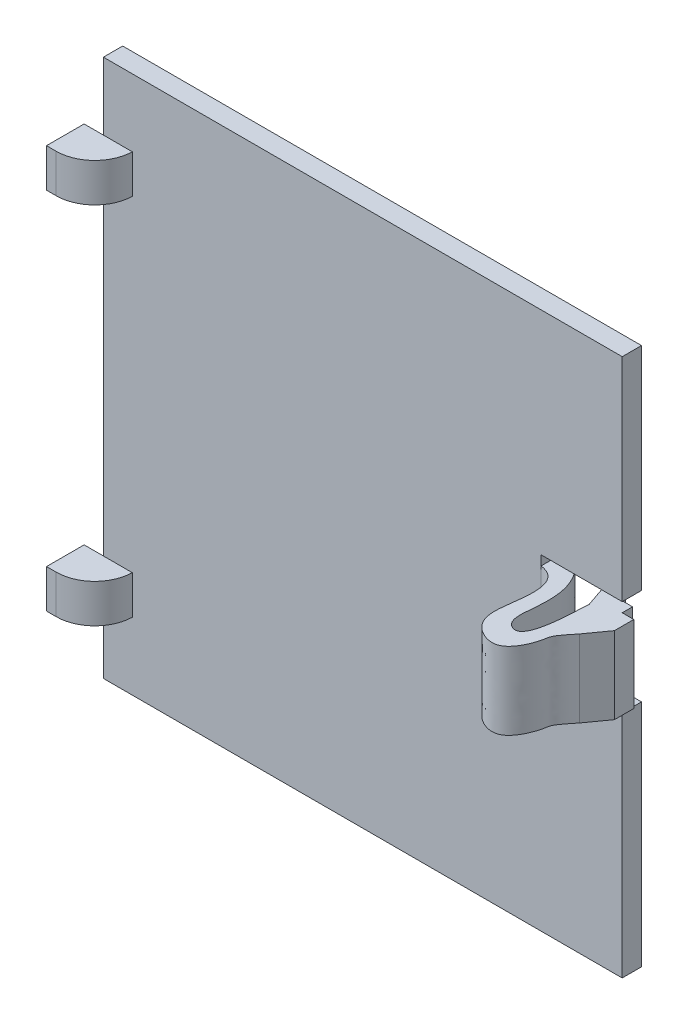
SolidWorks part; units mm, degrees
ref_plane "Plan de face" through (0, 0, 0) normal (0, 0, 1) x (1, 0, 0)
ref_plane "Plan de dessus" through (0, 0, 0) normal (0, 1, 0) x (1, 0, 0)
ref_plane "Plan de droite" through (0, 0, 0) normal (1, 0, 0) x (0, 0, -1)
sketch "Esquisse1" plane through (0, 0, 0) normal (0, 0, 1) x (1, 0, 0)
  line L1 (0, 0) -> (53.8, 0)
  line L2 (0, 0) -> (0, 55.8)
  line L3 (0, 55.8) -> (53.8, 55.8)
  line L4 (53.8, 0) -> (53.8, 55.8)
  dimension "D1" = 53.8
  dimension "D2" = 55.8
extrude "Boss.-Extru.1" add sketch "Esquisse1" along normal blind 2
sketch "Esquisse3" plane through (0, 0, 2) normal (0, 0, 1) x (1, 0, 0)
  line L0 (0, 55.8) -> (0, 0) construction
  line L1 (3, 7) -> (-2, 7)
  line L2 (3, 7) -> (3, 11)
  line L3 (3, 11) -> (-2, 11)
  line L4 (-2, 7) -> (-2, 11)
  line L5 (3, 44.8) -> (-2, 44.8)
  line L6 (3, 44.8) -> (3, 48.8)
  line L7 (3, 48.8) -> (-2, 48.8)
  line L8 (-2, 44.8) -> (-2, 48.8)
  line L9 (53.8, 55.8) -> (0, 55.8) construction
  line L10 (0, 0) -> (53.8, 0) construction
  dimension "D1" = 5
  dimension "D2" = 3
  dimension "D3" = 5
  dimension "D4" = 3
  dimension "D5" = 4
  dimension "D6" = 4
  dimension "D7" = 7
  dimension "D8" = 7
extrude "Boss.-Extru.2" add sketch "Esquisse3" along normal blind 3.9
fillet "Congé1" radius 4 2 edges at (3, 46.8, 5.9) (3, 9, 5.9)
sketch "Esquisse4" plane through (0, 0, 2) normal (0, 0, 1) x (1, 0, 0)
  line L0 (53.8, 0) -> (53.8, 55.8) construction
  line L1 (53.8, 33.8) -> (45.3874, 33.8)
  line L2 (53.8, 33.8) -> (53.8, 23.8)
  line L3 (53.8, 23.8) -> (45.3874, 23.8)
  line L4 (45.3874, 33.8) -> (45.3874, 23.8)
  line L5 (53.8, 55.8) -> (0, 55.8) construction
  dimension "D1" = 10
  dimension "D2" = 22
extrude "Enlèv. mat.-Extru.1" cut sketch "Esquisse4" against normal blind 7.8
sketch "Esquisse5" plane through (0, 33.8, 0) normal (0, -1, 0) x (1, 0, 0)
  line L0 (52.1165, 0.9275) -> (52.1165, 0)
  line L1 (0, 0) -> (53.8, 0) construction
  line L2 (52.1165, 0) -> (50.314, 0)
  line L3 (50.314, 0) -> (51.3364, 2.9673)
  line L4 (52.1165, 0.9275) -> (53.8, 0.9275)
  line L5 (53.8, 2) -> (53.8, 0) construction
  line L6 (53.8, 0.9275) -> (53.8, 2)
  line L7 (53.8, 2) -> (55, 2)
  line L8 (55, 2) -> (55, 4)
  line L9 (55, 4) -> (53.4886, 6.1084)
  line L10 (45.3874, 2) -> (45.3874, 0)
  spline S0 degree 3 poles (45.3874, 0) (46.455, 0.0308) (47.1256, -0.0213) (48.8996, 2.4805) (48.9573, 5.3687) (48.4914, 8.6027) (50.0819, 9.3139) (51.3612, 7.4414) (51.2508, 3.2239) (51.3364, 2.9673) knots 0 0 0 0 0.100125 0.177204 0.427984 0.587008 0.626059 0.727291 1 1 1 1
  spline S1 degree 3 poles (45.3874, 2) (47.5717, 2.2817) (47.4148, 6.0359) (46.5882, 10.3562) (50.8437, 12.3111) (52.4481, 7.8955) (52.0808, 7.8083) (53.4886, 6.1084) knots 0 0 0 0 0.293068 0.50878 0.665231 0.849912 1 1 1 1
  dimension "D1" = 2
  dimension "D2" = 2
  dimension "D3" = 1.2
extrude "Boss.-Extru.3" add sketch "Esquisse5" along normal blind 8 from offset 1 contours S0 L3 L2 L0 L4 L6 L7 L8 L9 S1 L10
